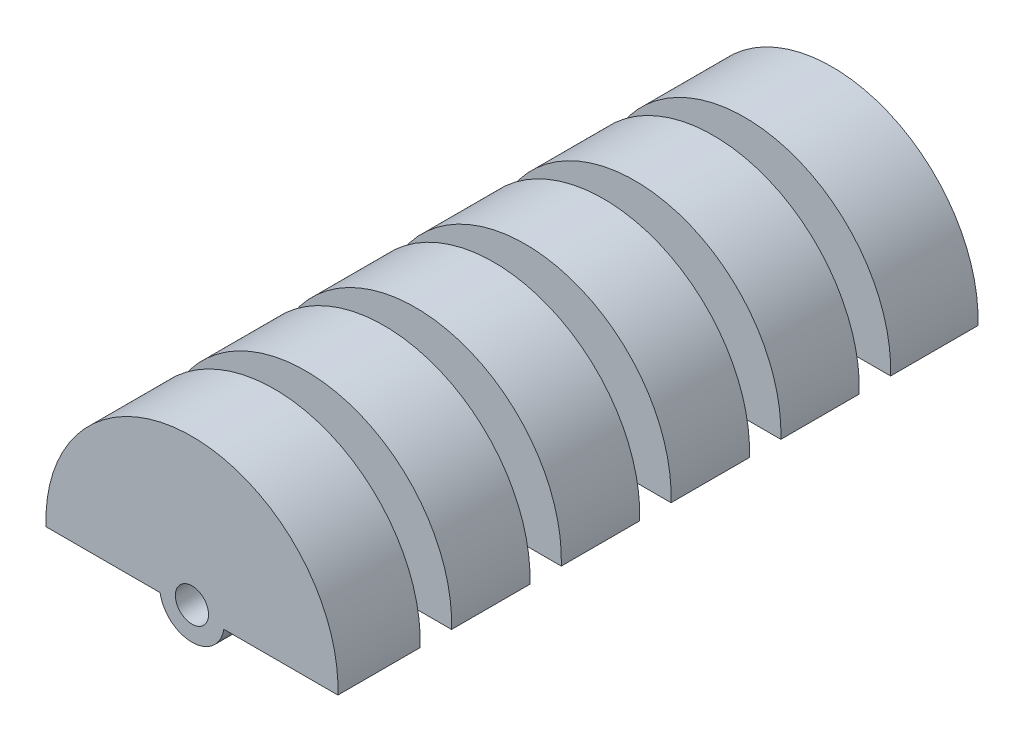
SolidWorks part; units mm, degrees
material "RUBBER 65A Test Modulus"
ref_plane "Front Plane" through (0, 0, 0) normal (0, 0, 1) x (1, 0, 0)
ref_plane "Top Plane" through (0, 0, 0) normal (0, 1, 0) x (1, 0, 0)
ref_plane "Right Plane" through (0, 0, 0) normal (1, 0, 0) x (0, 0, -1)
sketch "Sketch3" plane through (0, 0, 0) normal (0, 0, 1) x (1, 0, 0)
  circle A0 centre (0, 0) radius 27.94
  dimension "D1" = 55.88
extrude "Boss-Extrude2" add sketch "Sketch3" along normal blind 122.46
ref_axis "Axis2" through (0, 0, 121.5887) along (0, 0, -1)
sketch "Sketch5" plane through (0, 0, 122.46) normal (0, 0, 1) x (1, 0, 0)
  circle A0 centre (0, 0) radius 3.175
  dimension "D1" = 6.35
extrude "Cut-Extrude1" cut sketch "Sketch5" against normal through all contours A0
sketch "Sketch4" plane through (0, 0, 0) normal (0, 1, 0) x (1, 0, 0)
  line L0 (0, -122.46) -> (0, 0) construction
  line L1 (-27.94, -122.46) -> (27.94, -122.46) construction
  line L3 (-27.94, -106.72) -> (-13.94, -106.72)
  line L4 (-27.94, -106.72) -> (-27.94, -100.72)
  line L5 (-27.94, -100.72) -> (-13.94, -100.72)
  line L6 (-13.94, -106.72) -> (-13.94, -100.72)
  line L63 (-27.94, -85.72) -> (-27.94, -79.72)
  line L64 (-27.94, -85.72) -> (-13.94, -85.72)
  line L65 (-13.94, -85.72) -> (-13.94, -79.72)
  line L66 (-27.94, -79.72) -> (-13.94, -79.72)
  line L67 (-27.94, -64.72) -> (-27.94, -58.72)
  line L68 (-27.94, -64.72) -> (-13.94, -64.72)
  line L69 (-13.94, -64.72) -> (-13.94, -58.72)
  line L70 (-27.94, -58.72) -> (-13.94, -58.72)
  line L71 (-27.94, -43.72) -> (-27.94, -37.72)
  line L72 (-27.94, -43.72) -> (-13.94, -43.72)
  line L73 (-13.94, -43.72) -> (-13.94, -37.72)
  line L74 (-27.94, -37.72) -> (-13.94, -37.72)
  line L75 (-27.94, -22.72) -> (-27.94, -16.72)
  line L76 (-27.94, -22.72) -> (-13.94, -22.72)
  line L77 (-13.94, -22.72) -> (-13.94, -16.72)
  line L78 (-27.94, -16.72) -> (-13.94, -16.72)
  line L91 (-27.94, -106.72) -> (-27.94, -85.72) construction
  line L92 (-27.94, -1.72) -> (-27.94, 4.28) [skipped]
  line L93 (-27.94, -1.72) -> (-13.94, -1.72) [skipped]
  line L94 (-13.94, -1.72) -> (-13.94, 4.28) [skipped]
  line L95 (-27.94, 4.28) -> (-13.94, 4.28) [skipped]
  line L96 (-27.94, 19.28) -> (-27.94, 25.28) [skipped]
  line L97 (-27.94, 19.28) -> (-13.94, 19.28) [skipped]
  line L98 (-13.94, 19.28) -> (-13.94, 25.28) [skipped]
  line L99 (-27.94, 25.28) -> (-13.94, 25.28) [skipped]
  line L100 (-27.94, 40.28) -> (-27.94, 46.28) [skipped]
  line L101 (-27.94, 40.28) -> (-13.94, 40.28) [skipped]
  line L102 (-13.94, 40.28) -> (-13.94, 46.28) [skipped]
  line L103 (-27.94, 46.28) -> (-13.94, 46.28) [skipped]
  dimension "D1" = 15.74
  dimension "D2" = 6
  dimension "D3" = 27.94
  dimension "D4" = 14
  dimension "D6" = 21
  dimension "D5" = 8
revolve "Cut-Revolve1" cut sketch "Sketch4" angle 360 about L0
shell "Shell1" thickness 3
sketch "Sketch10" plane through (0, 0, 0) normal (0, 0, -1) x (-1, 0, 0)
  line L0 (0, 27.94) -> (0, -27.94) construction
  line L1 (-27.94, 0) -> (27.94, 0) construction
  line L2 (-1, 27.9221) -> (-1, 3.0134)
  line L3 (1, 3.0134) -> (1, 27.9221)
  line L4 (3.0134, 1) -> (27.9221, 1)
  line L5 (3.0134, -1) -> (27.9221, -1)
  line L6 (-1, -3.0134) -> (-1, -27.9221)
  line L7 (1, -3.0134) -> (1, -27.9221)
  line L8 (-27.9221, -1) -> (-3.0134, -1)
  line L9 (-27.9221, 1) -> (-3.0134, 1)
  circle A0 centre (0, 0) radius 27.94 construction
  circle A1 centre (0, 0) radius 3.175 construction
  arc A2 (-1, -27.9221) -> (1, -27.9221) centre (0, 0) ccw
  arc A3 (27.9221, -1) -> (27.9221, 1) centre (0, 0) ccw
  arc A4 (1, 27.9221) -> (-1, 27.9221) centre (0, 0) ccw
  arc A5 (-27.9221, 1) -> (-27.9221, -1) centre (0, 0) ccw
  arc A6 (-1, -3.0134) -> (1, -3.0134) centre (0, 0) ccw
  arc A7 (-3.0134, 1) -> (-3.0134, -1) centre (0, 0) ccw
  arc A8 (1, 3.0134) -> (-1, 3.0134) centre (0, 0) ccw
  arc A9 (3.0134, -1) -> (3.0134, 1) centre (0, 0) ccw
  dimension "D1" = 1
  dimension "D2" = 1
  dimension "D3" = 1
  dimension "D4" = 1
  dimension "D5" = 1
extrude "Boss-Extrude3" add sketch "Sketch10" against normal up to surface (122.46 mm away) up to face at (3.175, 0, 122.46)
ref_plane "Plane1" through (0, 0, 0) normal (-0.7071, -0.7071, 0) x (0, 0, -1)
ref_plane "Plane2" through (0, 0, 0) normal (-0.7071, 0.7071, 0) x (0, 0, -1)
ref_plane "Plane3" through (0, 0, 0) normal (0, 1, 0) x (1, 0, 0)
sketch "Sketch13" plane through (0, 0, 0) normal (0, 1, 0) x (1, 0, 0)
  line L0 (-30.3872, -37.72) -> (-13.9041, -37.72)
  line L1 (-30.3872, -16.72) -> (-13.9041, -16.72)
  line L2 (-30.3872, -16.72) -> (-30.3872, -22.72)
  line L3 (-30.3872, -22.72) -> (-13.9041, -22.72)
  line L4 (-13.9041, -16.72) -> (-13.9041, -22.72)
  line L5 (-30.3872, -37.72) -> (-30.3872, -43.72)
  line L6 (-30.3872, -43.72) -> (-13.9041, -43.72)
  line L7 (-13.9041, -37.72) -> (-13.9041, -43.72)
  line L8 (-30.3872, -58.72) -> (-13.9041, -58.72)
  line L9 (-30.3872, -58.72) -> (-30.3872, -64.72)
  line L10 (-30.3872, -64.72) -> (-13.9041, -64.72)
  line L11 (-13.9041, -58.72) -> (-13.9041, -64.72)
  line L12 (-30.3872, -79.72) -> (-13.9041, -79.72)
  line L13 (-30.3872, -79.72) -> (-30.3872, -85.72)
  line L14 (-30.3872, -85.72) -> (-13.9041, -85.72)
  line L15 (-13.9041, -79.72) -> (-13.9041, -85.72)
  line L16 (-30.3872, -100.72) -> (-13.9041, -100.72)
  line L17 (-30.3872, -100.72) -> (-30.3872, -106.72)
  line L18 (-30.3872, -106.72) -> (-13.9041, -106.72)
  line L19 (-13.9041, -100.72) -> (-13.9041, -106.72)
  dimension "D2" = 6
  dimension "D1" = 5
revolve "Cut-Revolve2" cut sketch "Sketch13" angle 360 about axis through (0, 0, 121.5887) along (0, 0, -1)
sketch "Sketch15" plane through (0, 0, 0) normal (0, 0, -1) x (-1, 0, 0)
  line L0 (0, 0) -> (0, 28.5004) construction
  line L1 (0, 0) -> (-22.0052, 22.0052) construction
sketch "Sketch16" plane through (0, 0, 0) normal (0, 0, -1) x (-1, 0, 0)
  line L0 (-3.175, 0) -> (-6.9755, 0) construction
  line L1 (-27.94, 0) -> (27.94, 0) construction
  line L2 (3.175, 0) -> (7.175, 0) construction
  line L3 (-6.9755, 0) -> (-6.9755, -0.971) construction
  line L4 (-6.9755, -0.971) -> (-6.6911, -0.971) construction
  line L5 (7.175, 0) -> (7.175, -1) construction
  line L8 (-3.175, 0) -> (-6.175, 0) construction
  line L9 (3.175, 0) -> (6.175, 0) construction
  line L10 (-27.9231, -0.971) -> (-6.0982, -0.971)
  line L11 (27.9221, -1) -> (6.0935, -1)
  arc A0 (-27.9231, -0.971) -> (27.9221, -1) centre (0, 0) ccw
  circle A1 centre (0, 0) radius 27.94 construction
  circle A2 centre (0, 0) radius 3.175 construction
  arc A5 (-6.0982, -0.971) -> (6.0935, -1) centre (0, 0) ccw
extrude "Cut-Extrude3" cut sketch "Sketch16" against normal blind 123
equation "\"inwall\"= .75"
equation "\"outwall\"=2"
